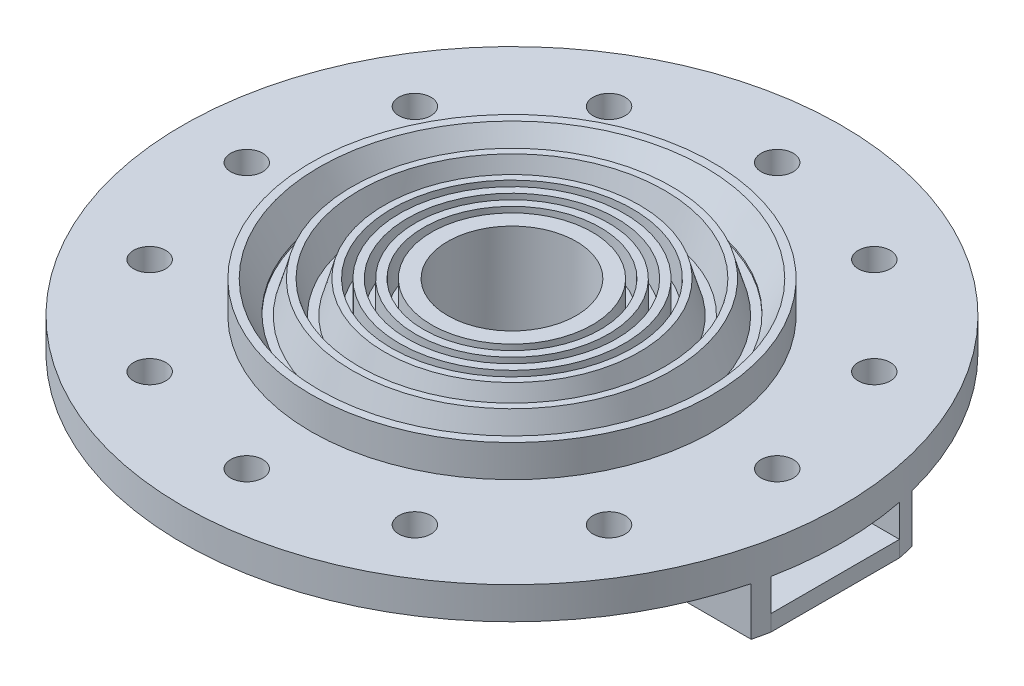
SolidWorks part; units mm, degrees
ref_plane "Front Plane" through (0, 0, 0) normal (0, 0, 1) x (1, 0, 0)
ref_plane "Top Plane" through (0, 0, 0) normal (0, 1, 0) x (1, 0, 0)
ref_plane "Right Plane" through (0, 0, 0) normal (1, 0, 0) x (0, 0, -1)
sketch "Sketch1" plane through (0, 0, 0) normal (0, 1, 0) x (1, 0, 0)
  line L0 (0, 15.875) -> (63.1218, 15.875)
  line L1 (0, 15.875) -> (0, 12.7)
  line L2 (0, -15.875) -> (0, -12.7)
  line L3 (0, 12.7) -> (63.8365, 12.7)
  line L4 (0, -12.7) -> (63.8365, -12.7)
  line L13 (0, -15.875) -> (63.1218, -15.875)
  circle A0 centre (0, 0) radius 39.6875
  circle A1 centre (0, 0) radius 30.1625
  circle A2 centre (0, 0) radius 31.75
  circle A3 centre (0, 0) radius 36.5125
  circle A4 centre (0, 0) radius 25.4
  circle A5 centre (0, 0) radius 23.8125
  circle A6 centre (0, 0) radius 15.875
  circle A7 centre (0, 0) radius 12.7
  circle A8 centre (0, 0) radius 65.0875
  circle A9 centre (0, 0) radius 22.225
  circle A10 centre (-26.1938, 45.3689) radius 3.175
  circle A11 centre (0, 52.3875) radius 3.175
  circle A12 centre (26.1937, 45.3689) radius 3.175
  circle A13 centre (45.3689, 26.1938) radius 3.175
  circle A14 centre (52.3875, 0) radius 3.175
  circle A15 centre (-45.3689, 26.1937) radius 3.175
  circle A16 centre (0, 0) radius 33.3375
  circle A17 centre (0, 0) radius 34.925
  circle A18 centre (0, 0) radius 28.575
  circle A19 centre (0, 0) radius 26.9875
  circle A20 centre (-52.3875, 0) radius 3.175
  circle A21 centre (-45.3689, -26.1938) radius 3.175
  circle A22 centre (-26.1937, -45.3689) radius 3.175
  circle A23 centre (0, -52.3875) radius 3.175
  circle A24 centre (26.1938, -45.3689) radius 3.175
  circle A25 centre (45.3689, -26.1937) radius 3.175
  circle A26 centre (0, 0) radius 20.6375
  circle A27 centre (0, 0) radius 19.05
  circle A28 centre (0, 0) radius 17.4625
extrude "Boss-Extrude2" add sketch "Sketch1" along normal blind 12.7 contours A3 L0 A0 L13 | A17 L0 A3 L13 | L0 A16 L13 A2 | L0 A2 L13 A1 | A18 L0 A1 L13 | L0 A19 L13 A4 | A5 L0 A4 L13 | A7 L1 A6 L2 | L3 A6 L1 | A7 L4 A6 L3 | L2 A6 L4 | A5 L13 A4 L4 | L13 A19 L4 A4 | A18 L13 A1 L4 | L13 A2 L4 A1 | L13 A16 L4 A2 | A17 L13 A3 L4 | A3 L13 A0 L4 | A3 L4 A0 L3 | A17 L4 A3 L3 | L4 A16 L3 A2 | L4 A2 L3 A1 | A18 L4 A1 L3 | L4 A19 L3 A4 | A5 L4 A4 L3 | A5 L3 A4 L0 | L3 A19 L0 A4 | A18 L3 A1 L0 | L3 A2 L0 A1 | L3 A16 L0 A2 | A17 L3 A3 L0 | A3 L3 A0 L0 region at (3.6248, 0, -13.9816) region at (-0.355, 0, -14.2875) region at (4.7625, 0, -12.4005) region at (3.6248, 0, 13.9816) region at (-24.4927, 0, 0) region at (19.9716, 0, -14.3177) region at (-26.1277, 0, 0) region at (21.904, 0, -14.3126) region at (21.0701, 0, -12.4406) region at (19.9716, 0, 14.3177) region at (22.9048, 0, -12.4411) region at (21.904, 0, 14.3126) region at (-29.3968, 0, 0) region at (25.6235, 0, -14.3058) region at (-31.031, 0, 0) region at (27.4309, 0, -14.3035) region at (26.4781, 0, -12.4419) region at (25.6235, 0, 14.3058) region at (-32.6649, 0, 0) region at (29.2124, 0, -14.3016) region at (28.2289, 0, -12.4422) region at (27.4309, 0, 14.3035) region at (29.9615, 0, -12.4425) region at (29.2124, 0, 14.3016) region at (-35.9324, 0, 0) region at (32.7147, 0, -14.2987) region at (-37.6119, 0, 0) region at (35.296, 0, -14.2972) region at (34.9369, 0, 0) region at (32.7147, 0, 14.2987) region at (37.3695, 0, 0) region at (35.296, 0, 14.2972)
chamfer "Chamfer1" distance 3.175 angle 62 1 edges at (0, 12.7, 34.925) first distance on face at (0, 12.7, 39.6875)
chamfer "Chamfer2" distance 6.35 angle 16 1 edges at (0, 12.7, 33.3375) first distance on face at (0, 12.7, 33.3375)
chamfer "Chamfer3" distance 1.5875 angle 76 1 edges at (0, 12.7, 28.575) first distance on face at (0, 12.7, 31.5167)
chamfer "Chamfer4" distance 6.35 angle 16 1 edges at (0, 12.7, 26.9875) first distance on face at (0, 12.7, 26.9875)
extrude "Boss-Extrude3" add sketch "Sketch1<20>" along normal blind 6.35 contours L0 A8 L13 A0 A25 A24 A23 A22 A21 A20 A15 A13 A12 A11 A10 | L13 A8 L4 A0 | L4 A8 L3 A0 A14 | L3 A8 L0 A0 | L0 A17 L13 A16 | A19 L0 A18 L13 | L13 A17 L4 A16 | L4 A17 L3 A16 | L3 A17 L0 A16 | A19 L3 A18 L0 | A19 L4 A18 L3 | A19 L13 A18 L4 | A9 L13 A5 L4 | A27 L13 A26 L4 | L13 A28 L4 A6 | L4 A28 L3 A6 | A27 L4 A26 L3 | A9 L4 A5 L3 | A9 L0 A5 L13 | A27 L0 A26 L13 | L0 A28 L13 A6 | A9 L3 A5 L0 | A27 L3 A26 L0 | L3 A28 L0 A6 region at (-16.303, 0, 0) region at (7.7398, 0, -14.5099) region at (7.7398, 0, 14.5099) region at (10.7552, 0, -12.4339) region at (-19.5836, 0, 0) region at (13.6102, 0, -14.3531) region at (15.233, 0, -12.438) region at (13.6102, 0, 14.3531) region at (-22.8571, 0, 0) region at (17.9686, 0, -14.3249) region at (19.1911, 0, -12.44) region at (17.9686, 0, 14.3249) region at (-27.7624, 0, 0) region at (23.784, 0, -14.3088) region at (24.7051, 0, -12.4416) region at (23.784, 0, 14.3088) region at (-34.2987, 0, 0) region at (30.9725, 0, -14.3) region at (31.6789, 0, -12.4427) region at (30.9725, 0, 14.3) region at (-41.5146, 0, 0) region at (50.2517, 0, -14.2926) region at (50.7185, 0, -12.3257) region at (50.2517, 0, 14.2926)
sketch "Sketch1<20>" plane through (0, 0, 0) normal (0, 1, 0) x (1, 0, 0) same geometry as "Sketch1"
extrude "Boss-Extrude4" add sketch "Sketch1<21>" along normal blind 12.7 contours A28 L4 A27 L3 | A26 L4 A9 L3 | A26 L13 A9 L4 | A28 L13 A27 L4 | A26 L0 A9 L13 | A28 L0 A27 L13 | A28 L3 A27 L0 | A26 L3 A9 L0 region at (-17.9448, 0, 0) region at (11.0831, 0, -14.3875) region at (13.0922, 0, -12.4364) region at (11.0831, 0, 14.3875) region at (-21.2209, 0, 0) region at (15.8658, 0, -14.3356) region at (17.253, 0, -12.4391) region at (15.8658, 0, 14.3356)
sketch "Sketch1<21>" plane through (0, 0, 0) normal (0, 1, 0) x (1, 0, 0) same geometry as "Sketch1"
extrude "Boss-Extrude6" add sketch "Sketch1<24>" against normal blind 6.35 contours L3 A8 L0 A0 | A3 L3 A0 L0 | A17 L3 A3 L0 | L3 A17 L0 A16 | L3 A16 L0 A2 | L3 A2 L0 A1 | A18 L3 A1 L0 | A19 L3 A18 L0 | L3 A19 L0 A4 | A5 L3 A4 L0 | A9 L3 A5 L0 | A26 L3 A9 L0 | A27 L3 A26 L0 | A28 L3 A27 L0 | L3 A28 L0 A6 | L3 A6 L1 | A7 L1 A6 L2 | L2 A6 L4 | L13 A28 L4 A6 | A28 L13 A27 L4 | A27 L13 A26 L4 | A26 L13 A9 L4 | A9 L13 A5 L4 | A5 L13 A4 L4 | L13 A19 L4 A4 | A19 L13 A18 L4 | A18 L13 A1 L4 | L13 A2 L4 A1 | L13 A16 L4 A2 | L13 A17 L4 A16 | A17 L13 A3 L4 | A3 L13 A0 L4 | L13 A8 L4 A0 region at (3.6248, 0, -13.9816) region at (-0.355, 0, -14.2875) region at (7.7398, 0, -14.5099) region at (11.0831, 0, -14.3875) region at (7.7398, 0, 14.5099) region at (3.6248, 0, 13.9816) region at (13.6102, 0, -14.3531) region at (11.0831, 0, 14.3875) region at (15.8658, 0, -14.3356) region at (13.6102, 0, 14.3531) region at (17.9686, 0, -14.3249) region at (15.8658, 0, 14.3356) region at (19.9716, 0, -14.3177) region at (17.9686, 0, 14.3249) region at (21.904, 0, -14.3126) region at (19.9716, 0, 14.3177) region at (23.784, 0, -14.3088) region at (21.904, 0, 14.3126) region at (25.6235, 0, -14.3058) region at (23.784, 0, 14.3088) region at (27.4309, 0, -14.3035) region at (25.6235, 0, 14.3058) region at (29.2124, 0, -14.3016) region at (27.4309, 0, 14.3035) region at (30.9725, 0, -14.3) region at (29.2124, 0, 14.3016) region at (32.7147, 0, -14.2987) region at (30.9725, 0, 14.3) region at (35.296, 0, -14.2972) region at (32.7147, 0, 14.2987) region at (50.2517, 0, -14.2926) region at (35.296, 0, 14.2972) region at (50.2517, 0, 14.2926)
sketch "Sketch1<24>" plane through (0, 0, 0) normal (0, 1, 0) x (1, 0, 0) same geometry as "Sketch1"
sketch "Sketch2" plane through (0, -6.35, 0) normal (0, -1, 0) x (-1, 0, 0)
  line L0 (0, 12.7) -> (-63.8365, 12.7)
  line L1 (0, 15.875) -> (-63.1218, 15.875)
  line L2 (0, -12.7) -> (-63.8365, -12.7)
  line L3 (0, -15.875) -> (-63.5, -15.875)
  line L4 (0, -15.875) -> (-63.1218, -15.875) construction
  line L6 (-63.1218, 15.875) -> (0, 15.875)
  line L7 (-63.1218, 15.875) -> (-63.1218, -15.875)
  line L8 (-63.1218, -15.875) -> (0, -15.875)
  line L9 (0, 15.875) -> (0, -15.875)
  line L10 (-63.8365, 12.7) -> (0, 12.7)
  line L11 (-63.8365, 12.7) -> (-63.8365, -12.7)
  line L12 (-63.8365, -12.7) -> (0, -12.7)
  line L13 (0, 12.7) -> (0, -12.7)
  circle A0 centre (0, 0) radius 12.7
  circle A1 centre (0, 0) radius 15.875
  line M5 (-63.8365, 12.7) -> (0, 12.7)
  arc M6 (0, 12.7) -> (0, -12.7) centre (0, 0) cw
  line M7 (0, -12.7) -> (-63.8365, -12.7)
  arc M8 (-63.8365, -12.7) -> (-63.1218, -15.875) centre (0, 0) ccw
  line M9 (-63.1218, -15.875) -> (0, -15.875)
  arc M10 (0, -15.875) -> (0, 15.875) centre (0, 0) ccw
  line M11 (0, 15.875) -> (-63.1218, 15.875)
  arc M12 (-63.1218, 15.875) -> (-63.8365, 12.7) centre (0, 0) ccw
extrude "Boss-Extrude7" add sketch "Sketch2" along normal blind 3.175 contours A1 L0 L7 L12 | L11 L2 L7 M5 | L7 M12 M5 | L7 L2 M8 | A1 L12 L7 M9 | A1 L7 L0 M11 | L9 M10 M6 | L10 A1 A0 M7 | L9 A1 L10 | A1 L9 M7 | L9 M6 | L9 A0 region at (12.9995, -6.35, 0) region at (3.6248, -6.35, -13.9816) region at (-5.39, -6.35, 0) region at (-0.355, -6.35, -14.2875) region at (5.39, -6.35, 0) region at (38.509, -6.35, 0) region at (34.7618, -6.35, -14.3226) region at (3.6248, -6.35, 13.9816) region at (63.4791, -6.35, 0) region at (63.3648, -6.35, -13.7782) region at (34.7618, -6.35, 14.3226) region at (63.3648, -6.35, 13.7782)
sketch "Sketch4" plane through (0, -9.525, 0) normal (0, -1, 0) x (1, 0, 0)
  circle A0 centre (0, 0) radius 3.175
extrude "Cut-Extrude1" cut sketch "Sketch4" against normal blind 3.175
sketch "Sketch5" plane through (0, -9.525, 0) normal (0, -1, 0) x (1, 0, 0)
  circle A0 centre (0, 0) radius 6.35
extrude "Cut-Extrude2" cut sketch "Sketch5" against normal blind 1.5875
extrude "Cut-Extrude3" cut sketch "Sketch5<2>" against normal blind 12.7 contours A0
sketch "Sketch5<2>" plane through (0, -9.525, 0) normal (0, -1, 0) x (1, 0, 0) same geometry as "Sketch5"
